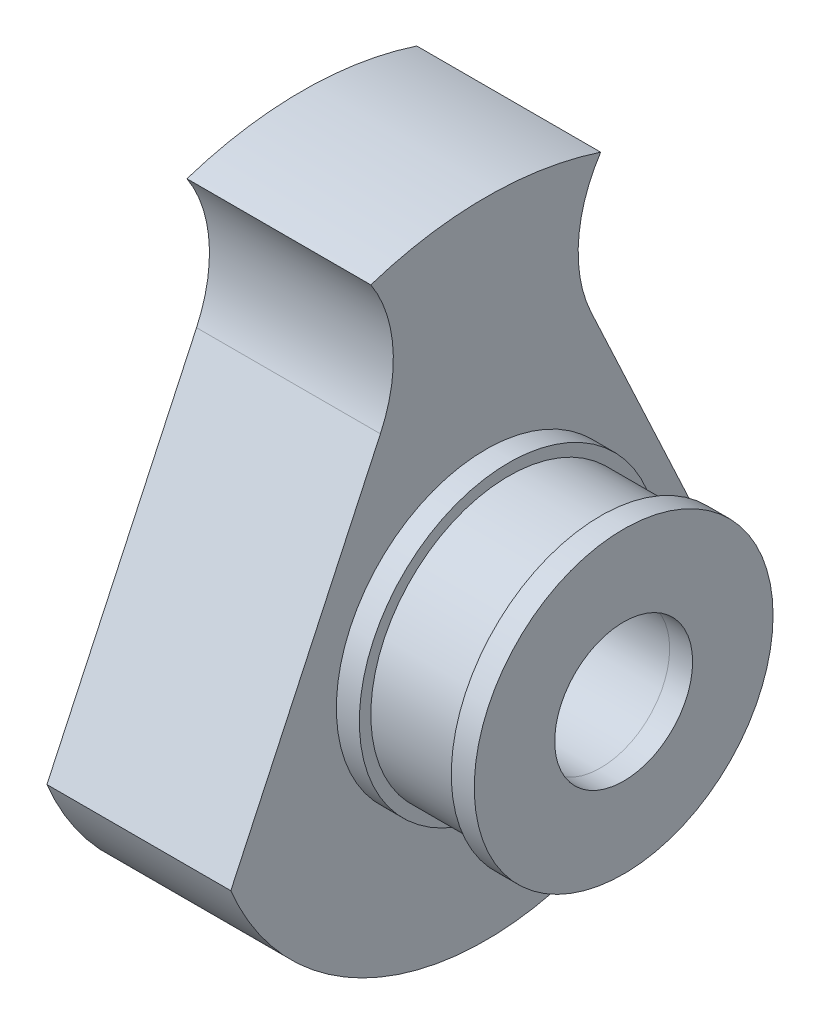
SolidWorks part; units mm, degrees
material "AISI Type A2 Tool Steel"
ref_plane "Front Plane" through (0, 0, 0) normal (0, 0, 1) x (1, 0, 0)
ref_plane "Top Plane" through (0, 0, 0) normal (0, 1, 0) x (1, 0, 0)
ref_plane "Right Plane" through (0, 0, 0) normal (1, 0, 0) x (0, 0, -1)
sketch "Sketch2" plane through (0, 0, 0) normal (1, 0, 0) x (0, 0, -1)
  circle A0 centre (0, 0) radius 50.8
  dimension "D1" = 101.6
extrude "Boss-Extrude1" add sketch "Sketch2" along normal mid plane 25.4
sketch "Sketch3" plane through (12.7, 0, 0) normal (1, 0, 0) x (0, 0, -1)
  line L0 (0, 0) -> (-15.875, 48.2558) construction
  line L1 (-15.875, 48.2558) -> (37.8761, -33.8533) construction
  line L2 (0, 0) -> (0, 50.8) construction
  line L3 (-15.875, 48.2558) -> (0, 48.2558) construction
  line L4 (-14.5484, 29.7711) -> (-41.8552, -28.7886)
  arc A0 (-15.875, 48.2558) -> (-14.5484, 29.7711) centre (-31.8135, 37.822) cw
  circle A1 centre (0, 0) radius 50.8 construction
  circle A3 centre (0, 0) radius 50.8
  arc A4 (-15.875, 48.2558) -> (-41.8552, -28.7886) centre (0, 0) ccw
  dimension "D3" = 19.05
  dimension "D2" = 15
  dimension "D4" = 15.875
  dimension "D5" = 25
  dimension "D1" = 0
extrude "Cut-Extrude1" cut sketch "Sketch3" against normal through all
mirror "Mirror1" about plane through (0, 0, 0) normal (0, 0, 1) of "Cut-Extrude1"
sketch "Sketch4" plane through (12.7, 0, 0) normal (1, 0, 0) x (0, 0, -1)
  line L2 (41.8552, -28.7886) -> (14.5484, 29.7711)
  line L3 (41.8552, -28.7886) -> (35.2139, -14.5462)
  line L4 (-14.5484, 29.7711) -> (-41.8552, -28.7886)
  line L5 (-35.2139, -14.5462) -> (-41.8552, -28.7886)
  arc A0 (-35.2139, -14.5462) -> (35.2139, -14.5462) centre (0, 0) ccw
  arc A7 (-41.8552, -28.7886) -> (41.8552, -28.7886) centre (0, 0) ccw
  arc A8 (15.875, 48.2558) -> (14.5484, 29.7711) centre (31.8135, 37.822) ccw
  arc A9 (15.875, 48.2558) -> (-15.875, 48.2558) centre (0, 0) ccw
  arc A10 (-14.5484, 29.7711) -> (-15.875, 48.2558) centre (-31.8135, 37.822) ccw
  arc A15 (-41.8552, -28.7886) -> (41.8552, -28.7886) centre (0, 0) ccw
  dimension "D2" = 38.1
  dimension "D1" = 0
extrude "Cut-Extrude2" cut sketch "Sketch4" against normal through all
sketch "Sketch7" plane through (12.7, 0, 0) normal (1, 0, 0) x (0, 0, -1)
  line L0 (-16.1607, 0) -> (-8.7581, 15.875)
  line L1 (-8.7581, 15.875) -> (8.7581, 15.875)
  line L2 (8.7581, 15.875) -> (16.1607, 0)
  line L3 (16.1607, 0) -> (8.7581, -15.875)
  line L4 (8.7581, -15.875) -> (-8.7581, -15.875)
  line L5 (-8.7581, -15.875) -> (-16.1607, 0)
  line L6 (-16.1607, 0) -> (0, 0) construction
  line L7 (0, 0) -> (16.1607, 0) construction
  line L8 (0, -15.875) -> (0, 0) construction
  line L9 (0, 0) -> (0, 15.875) construction
  line L10 (-35.2139, -14.5462) -> (-14.5484, 29.7711) construction
  dimension "D1" = 31.75
extrude "Cut-Extrude4" cut sketch "Sketch7" against normal blind 9.525
sketch "Sketch9" plane through (3.175, 0, 0) normal (1, 0, 0) x (0, 0, -1)
  line L7 (-16.0206, 0) -> (-8.6772, -15.748)
  line L8 (-8.6772, -15.748) -> (8.6772, -15.748)
  line L9 (8.6772, -15.748) -> (16.0206, 0)
  line L10 (16.0206, 0) -> (8.6772, 15.748)
  line L11 (8.6772, 15.748) -> (-8.6772, 15.748)
  line L12 (-8.6772, 15.748) -> (-16.0206, 0)
  line L13 (-16.1607, 0) -> (-8.7581, -15.875)
  line L14 (-8.7581, -15.875) -> (8.7581, -15.875)
  line L15 (8.7581, -15.875) -> (16.1607, 0)
  line L16 (16.1607, 0) -> (8.7581, 15.875)
  line L17 (8.7581, 15.875) -> (-8.7581, 15.875)
  line L18 (-8.7581, 15.875) -> (-16.1607, 0)
  line L19 (-16.1607, 0) -> (-8.7581, -15.875) construction
  line L20 (-8.7581, -15.875) -> (8.7581, -15.875) construction
  line L21 (8.7581, -15.875) -> (16.1607, 0) construction
  line L22 (16.1607, 0) -> (8.7581, 15.875) construction
  line L23 (8.7581, 15.875) -> (-8.7581, 15.875) construction
  line L24 (-8.7581, 15.875) -> (-16.1607, 0) construction
  dimension "D1" = 0
  dimension "D2" = 0.127
extrude "Boss-Extrude2" add sketch "Sketch9" along normal up to surface (9.525 mm away) separate body up to face at (12.7, 0, 0)
mirror "Mirror2" about plane through (0, 0, 0) normal (1, 0, 0) of "Cut-Extrude4"
mirror "Mirror3" about plane through (0, 0, 0) normal (1, 0, 0) of bodies 108
sketch "Sketch10" plane through (12.7, 0, 0) normal (1, 0, 0) x (0, 0, -1)
  circle A0 centre (0, 0) radius 20.6375
  dimension "D1" = 41.275
extrude "Boss-Extrude3" add sketch "Sketch10" along normal blind 3.175 separate body
sketch "Sketch11" plane through (15.875, 0, 0) normal (1, 0, 0) x (0, 0, -1)
  circle A0 centre (0, 0) radius 19.05
  dimension "D1" = 38.1
extrude "Boss-Extrude4" add sketch "Sketch11" along normal blind 12.7 separate body
sketch "Sketch12" plane through (28.575, 0, 0) normal (1, 0, 0) x (0, 0, -1)
  circle A0 centre (0, 0) radius 20.6375 construction
  circle A1 centre (0, 0) radius 20.6375
extrude "Boss-Extrude5" add sketch "Sketch12" along normal blind 3.175 separate body
sketch "Sketch5" plane through (12.7, 0, 0) normal (1, 0, 0) x (0, 0, -1)
  circle A0 centre (0, 0) radius 9.525
  circle A1 centre (0, 0) radius 6.35 construction
  dimension "D1" = 12.7
  dimension "D2" = 19.05
extrude "Cut-Extrude5" cut sketch "Sketch5" against normal through all both and the other way through all
